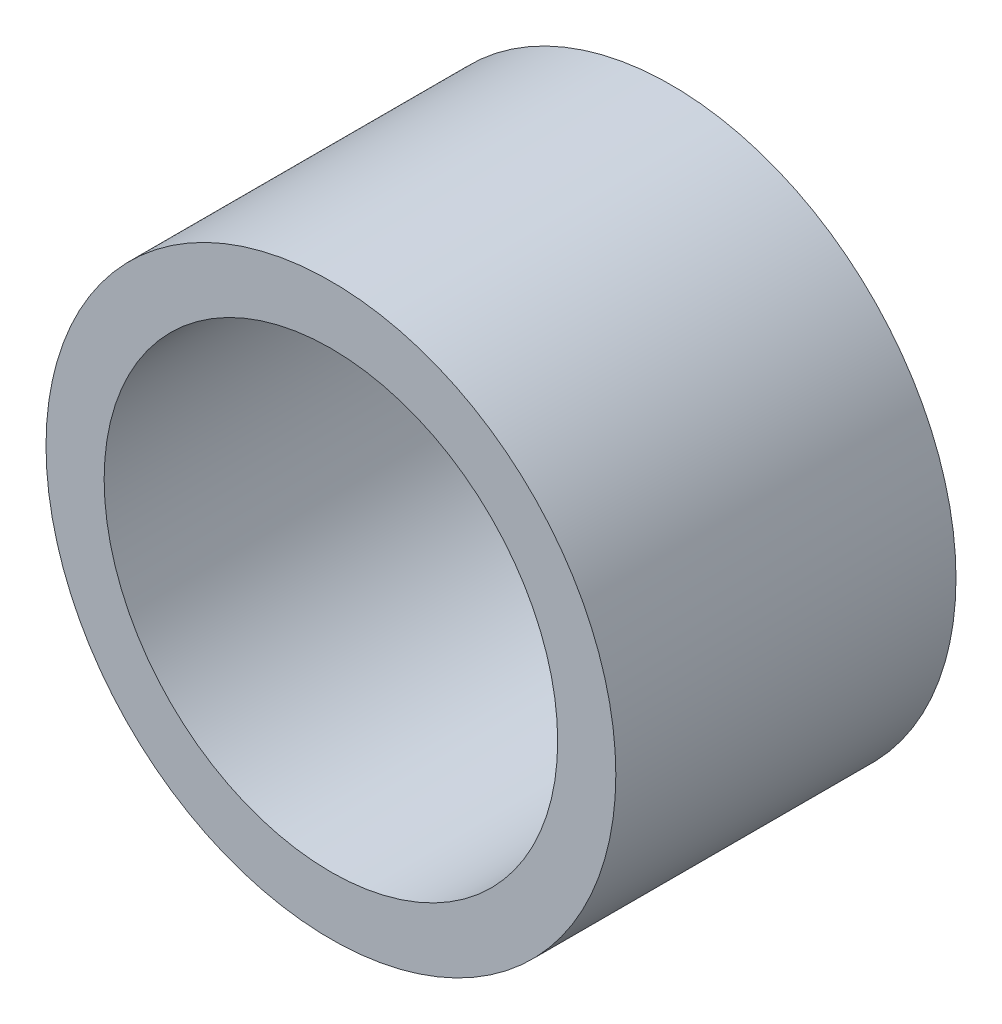
SolidWorks part; units mm, degrees
ref_plane "Front Plane" through (0, 0, 0) normal (0, 0, 1) x (1, 0, 0)
ref_plane "Top Plane" through (0, 0, 0) normal (0, 1, 0) x (1, 0, 0)
ref_plane "Right Plane" through (0, 0, 0) normal (1, 0, 0) x (0, 0, -1)
sketch "Sketch1" plane through (0, 0, 0) normal (0, 0, 1) x (1, 0, 0)
  circle A0 centre (0, 0) radius 5.0255 construction
  circle A1 centre (0, 0) radius 4 construction
  dimension "ID" = 8
  dimension "OD" = 10.051
sketch "Sketch2" plane through (0, 0, 0) normal (1, 0, 0) x (0, 0, -1)
  line L0 (-3, 0) -> (3, 0) construction
  dimension "Length" = 6
sketch "Sketch3" plane through (0, 0, 0) normal (0, 0, 1) x (1, 0, 0)
  circle A0 centre (0, 0) radius 4 construction
  circle A1 centre (0, 0) radius 5.0255 construction
  circle A2 centre (0, 0) radius 4
  circle A3 centre (0, 0) radius 5.0255
extrude "Boss-Extrude1" add sketch "Sketch3" along normal up to vertex (-3 mm away) and the other way up to vertex (-3 mm away) up to point (0, 0, -3) other way up to point (0, 0, 3)
ref_axis "Center Axis 1" through (0, 0, 1.65) along (0, 0, -1)
